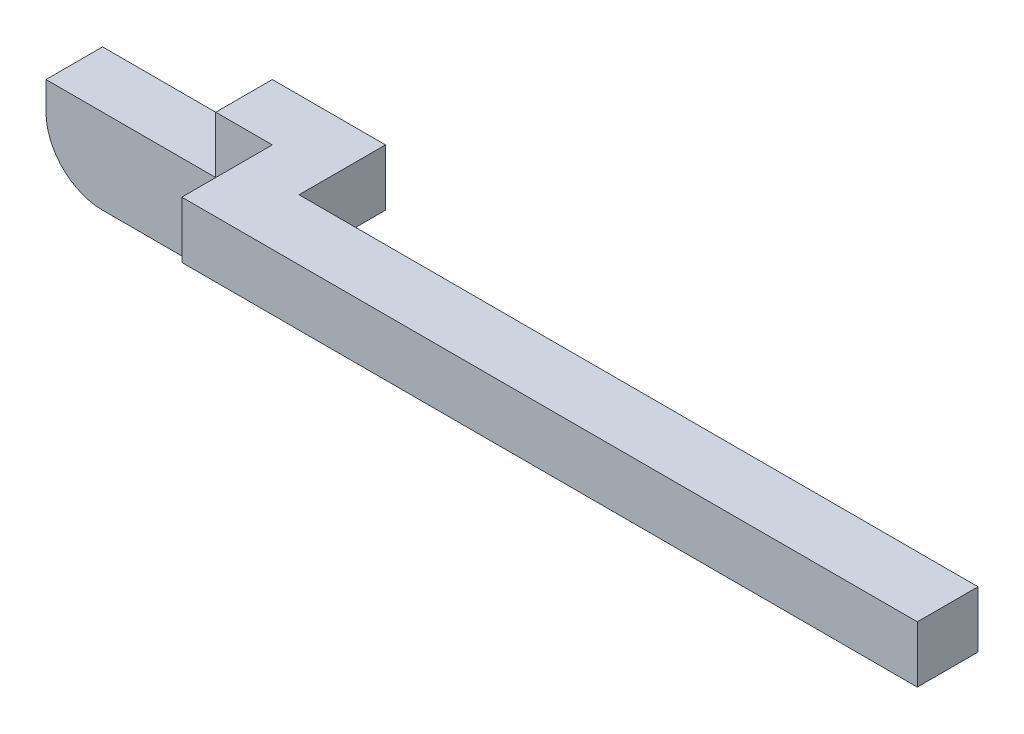
SolidWorks part; units mm, degrees
material "1060 Alloy"
ref_plane "Front Plane" through (0, 0, 0) normal (0, 0, 1) x (1, 0, 0)
ref_plane "Top Plane" through (0, 0, 0) normal (0, 1, 0) x (1, 0, 0)
ref_plane "Right Plane" through (0, 0, 0) normal (1, 0, 0) x (0, 0, -1)
ref_plane "Plane1" through (0, 0, 25.4) normal (0, 0, 1) x (1, 0, 0)
sketch "Sketch1" plane through (0, 0, 25.4) normal (0, 0, 1) x (1, 0, 0)
  line L0 (330.2, 25.4) -> (-101.6, 25.4)
  line L1 (-101.6, 25.4) -> (-101.6, -38.1)
  line L2 (-101.6, -38.1) -> (330.2, -38.1)
  line L3 (330.2, -38.1) -> (330.2, 25.4)
extrude "Boss-Extrude1" add sketch "Sketch1" against normal blind 25.4
sketch "Sketch2" plane through (0, 0, 0) normal (0, 0, -1) x (-1, 0, 0)
  line L0 (0, -38.1) -> (0, 0)
  line L1 (0, 0) -> (-330.2, 0)
  line L2 (-330.2, 0) -> (-330.2, -38.1)
  line L3 (-330.2, -38.1) -> (0, -38.1)
extrude "Cut-Extrude1" cut sketch "Sketch2" against normal through all
sketch "Sketch3" plane through (0, 0, 25.4) normal (0, 0, 1) x (1, 0, 0)
  line L0 (330.2, 0) -> (0, 0)
  line L1 (0, 0) -> (0, 25.4)
  line L2 (0, 25.4) -> (330.2, 25.4)
  line L3 (330.2, 25.4) -> (330.2, 0)
extrude "Boss-Extrude2" add sketch "Sketch3" along normal blind 40.64
sketch "Sketch4" plane through (0, 0, 25.4) normal (0, 0, 1) x (1, 0, 0)
  line L0 (-101.6, 0) -> (-25.4, 0)
  line L1 (-25.4, 0) -> (-25.4, 25.4)
  line L2 (-25.4, 25.4) -> (-101.6, 25.4)
  line L3 (-101.6, 25.4) -> (-101.6, 0)
extrude "Cut-Extrude2" cut sketch "Sketch4" against normal through all
sketch "Sketch5" plane through (0, 25.4, 0) normal (0, 1, 0) x (-1, 0, 0)
  line L0 (-25.4, -14.5507) -> (-25.4, 38.793)
  line L1 (-25.4, 38.793) -> (-352.766, 38.793)
  line L2 (-352.766, 38.793) -> (-352.766, -14.5507)
  line L3 (-352.766, -14.5507) -> (-25.4, -14.5507)
extrude "Cut-Extrude3" cut sketch "Sketch5" against normal through all
hole_wizard "Hole1" positions "Sketch7" profile "Sketch6" legacy
sketch "Sketch7" plane through (0, 0, 0) normal (0, 0, -1) x (-1, 0, 0)
  point P0 (-12.7, 12.7)
sketch "Sketch6" plane through (12.7, 12.7, 0) normal (1, 0, 0) x (0, 1, 0)
  line L0 (0, 0) -> (0, 5.08)
  line L1 (0, 5.08) -> (6.35, 5.08)
  line L2 (6.35, 5.08) -> (6.35, 0)
  line L3 (6.35, 0) -> (0, 0)
  line L4 (0, 110) -> (0, -10) construction
  dimension "Diameter" = 12.7
  dimension "Depth" = 5.08
fillet "Fillet1" radius 25.4 1 edges at (-101.6, -38.1, 12.7)
fillet "Fillet2" radius 25.4 1 edges at (0, -38.1, 12.7)
